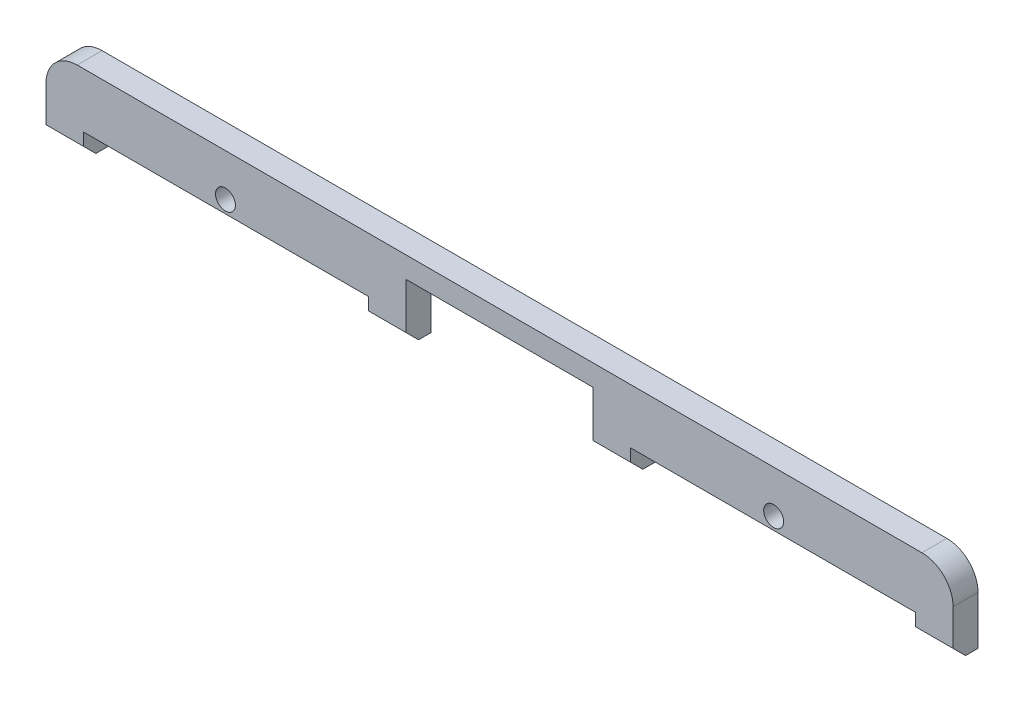
SolidWorks part; units mm, degrees
material "6061-T6 (SS)"
ref_plane "Front Plane" through (0, 0, 0) normal (0, 0, 1) x (1, 0, 0)
ref_plane "Top Plane" through (0, 0, 0) normal (0, 1, 0) x (1, 0, 0)
ref_plane "Right Plane" through (0, 0, 0) normal (1, 0, 0) x (0, 0, -1)
sketch "Sketch1" plane through (0, 0, 0) normal (1, 0, 0) x (0, 0, -1)
  line L0 (-3.0983, 0) -> (1.226, 0) construction
  line L1 (0, -3.2) -> (-2, -1.2)
  line L2 (0, -3.2) -> (0, 3.2)
  line L4 (-2, -1.2) -> (-2, 3.2)
  line L5 (-2, 3.2) -> (0, 3.2)
  dimension "D1" = 2
  dimension "D2" = 45
  dimension "D3" = 6.4
extrude "Boss-Extrude1" add sketch "Sketch1" along normal mid plane 72.8
fillet "Fillet3" radius 2.5 2 edges at (-36.4, 3.2, 1) (36.4, 3.2, 1)
sketch "Sketch5" [suppressed] plane through (-36.4, 0, 0) normal (-1, 0, 0) x (0, 0, 1)
  line L0 (0, -2.7) -> (2, -0.7)
  line L1 (0, -3.2) -> (0, 0.7) construction
  line L2 (2, 0.7) -> (2, -1.2) construction
  line L3 (2, -1.2) -> (0, -3.2) construction
  line L4 (2, -1.2) -> (2, -0.7)
  line L5 (2, -1.2) -> (0, -3.2)
  line L6 (0, -3.2) -> (0, -2.7)
  dimension "D1" = 0.5
extrude "Cut-Extrude5" [suppressed] cut sketch "Sketch5" against normal up to surface (72.8 mm away) up to face at (36.4, -0.75, 1)
sketch "Sketch7" [suppressed] plane through (-36.4, 0, 0) normal (-1, 0, 0) x (0, 0, 1)
  line L0 (0, -2.7) -> (-1, -1.7)
  line L1 (-1, -1.7) -> (-1, 3.2)
  line L2 (-1, 3.2) -> (0, 3.2)
  line L3 (0, 3.2) -> (0, -2.7)
  line L4 (0, 3.2) -> (2, 3.2) construction
  dimension "D1" = 45
  dimension "D2" = 3
extrude "Boss-Extrude2" [suppressed] add sketch "Sketch7" against normal up to surface (72.8 mm away) up to face at (36.4, -0.75, 1)
hole_wizard "M2x0.4 Tapped Hole1" positions "Sketch2" profile "Sketch3" tap size "M2x0.4" standard "ANSI Metric"
sketch "Sketch2" plane through (0, 0, 2) normal (0, 0, 1) x (1, 0, 0)
  circle A4 centre (-22, -0.2) radius 1.2 construction
  circle A5 centre (-22, -0.2) radius 1.2
  circle A8 centre (22, -0.2) radius 1.2 construction
  circle A9 centre (22, -0.2) radius 1.2
  circle A10 centre (0, -0.2) radius 1.2
  point P22 (-22, -0.2)
  point P28 (22, -0.2)
  point P31 (0, -0.2)
cosmetic thread "Hole Thread4" parameters "D1"=3, "D2"=2
cosmetic thread "Hole Thread6" parameters "D1"=3, "D2"=2
sketch "Sketch3" plane through (-22, -0.2, 2) normal (1, 0, 0) x (0, -1, 0)
  line L0 (0, 0) -> (0, 4.0807)
  line L1 (0, 4.0807) -> (0.8, 3.6)
  line L2 (0.8, 3.6) -> (0.8, 0)
  line L5 (0.8, 0) -> (0, 0)
  line L10 (0, 4.0807) -> (-0.8, 3.6) construction
  line L11 (0, -6.35) -> (0, 107.95) construction
  dimension "Tap Drill Dia." = 1.6
  dimension "Tap Drill Depth" = 3.6
  dimension "Drill Angle" = 118
cosmetic thread "Hole Thread7" parameters "D1"=3, "D2"=2
fillet "Fillet4" [suppressed] radius 2.5
sketch "Sketch4" plane through (0, 0, 0) normal (0, 0, 1) x (1, 0, 0)
  line L1 (7.5, 1.5) -> (-7.5, 1.5)
  line L2 (7.5, 1.5) -> (7.5, -3.2)
  line L3 (7.5, -3.2) -> (-7.5, -3.2)
  line L4 (-7.5, 1.5) -> (-7.5, -3.2)
  line L5 (0, 7.7759) -> (0, -8.8374) construction
  line L8 (-7.5, -1.7) -> (-7.5, -0.7) construction
  dimension "D1" = 4.7
extrude "Cut-Extrude4" cut sketch "Sketch4" along normal mid plane 10
sketch "Sketch8" plane through (36.4, 0, 0) normal (1, 0, 0) x (0, 0, -1)
  line L1 (-1, -3.2) -> (-2, -2.2)
  line L2 (-2, -2.2) -> (-2, -1.2)
  line L3 (-2, -1.2) -> (0, -3.2)
  line L4 (0, -3.2) -> (-1, -3.2)
  dimension "D1" = 1
extrude "Boss-Extrude3" add sketch "Sketch8" against normal blind 3
sketch "Sketch10" plane through (7.5, 0, 0) normal (-1, 0, 0) x (0, 0, 1)
  line L1 (1, -3.2) -> (2, -2.2)
  line L2 (2, -2.2) -> (2, -1.2)
  line L3 (2, -1.2) -> (0, -3.2)
  line L4 (2, -2.2) -> (1, -3.2) construction
  line L5 (0, -3.2) -> (1, -3.2)
extrude "Boss-Extrude5" add sketch "Sketch10" against normal blind 3
mirror "Mirror1" about plane through (0, 0, 0) normal (1, 0, 0) of "Boss-Extrude3", "Cut-Extrude4", "Boss-Extrude5"
sketch "Sketch11" [suppressed] plane through (36.4, 0, 0) normal (1, 0, 0) x (0, 0, -1)
  line L0 (0, -2.7) -> (-1, -2.7)
  line L1 (-1, -2.7) -> (-2, -1.7)
  line L2 (-2, -1.7) -> (-2, -0.7)
  line L3 (0, -2.7) -> (-2, -0.7)
  dimension "D1" = 1
extrude "Boss-Extrude6" [suppressed] add sketch "Sketch11" against normal blind 3 separate body
sketch "Sketch12" [suppressed] plane through (7.5, 0, 0) normal (-1, 0, 0) x (0, 0, 1)
  line L0 (0, -2.7) -> (1, -2.7)
  line L1 (1, -2.7) -> (2, -1.7)
  line L2 (2, -1.7) -> (2, -0.7)
  line L3 (0, -2.7) -> (2, -0.7)
  line L4 (1, -2.7) -> (0, -2.7) construction
  line L5 (2, -1.7) -> (1, -2.7) construction
extrude "Boss-Extrude7" [suppressed] add sketch "Sketch12" against normal blind 3
mirror "Mirror7" [suppressed] about plane through (0, 0, 0) normal (1, 0, 0) of bodies 112 111
